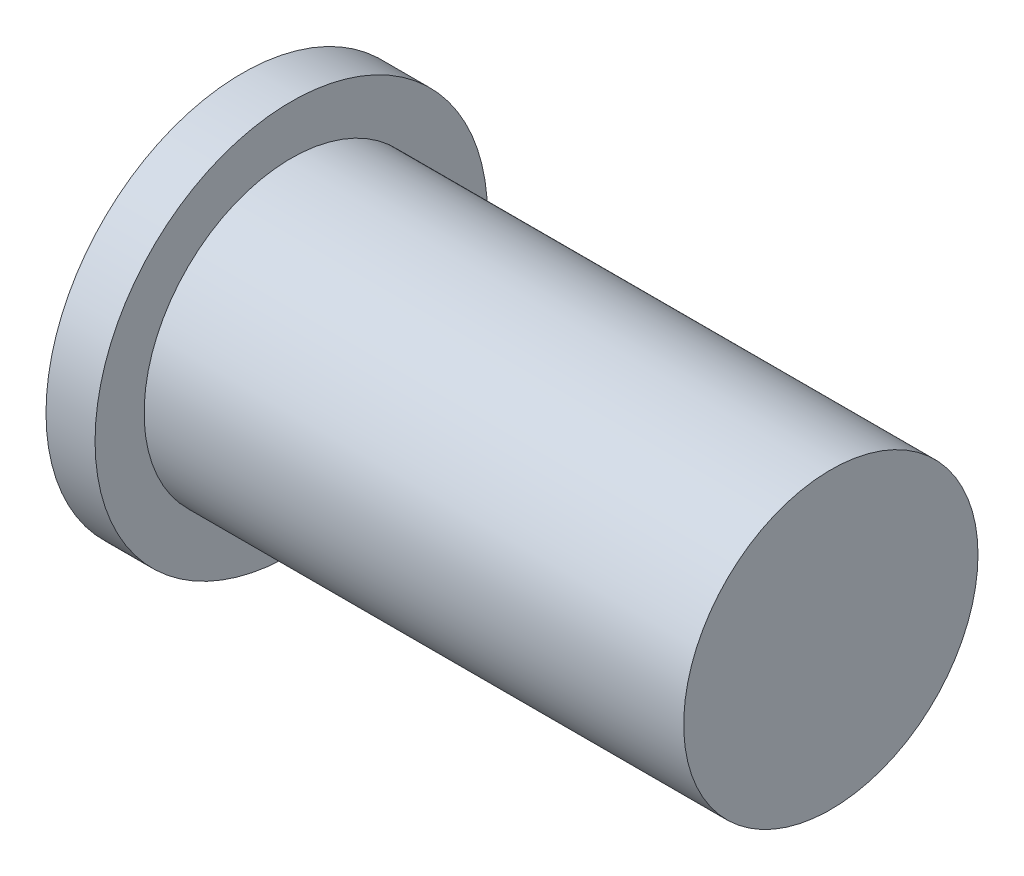
SolidWorks part; units mm, degrees
ref_plane "Front Plane" through (0, 0, 0) normal (0, 0, 1) x (1, 0, 0)
ref_plane "Top Plane" through (0, 0, 0) normal (0, 1, 0) x (1, 0, 0)
ref_plane "Right Plane" through (0, 0, 0) normal (1, 0, 0) x (0, 0, -1)
sketch "Sketch1" plane through (0, 0, 0) normal (1, 0, 0) x (0, 0, -1)
  circle A0 centre (0.1077, 0) radius 4
  circle A1 centre (0.1077, 0) radius 3
  dimension "D1" = 8
  dimension "D2" = 6
extrude "Boss-Extrude1" add sketch "Sketch1" along normal blind 1
extrude "Boss-Extrude2" add sketch "Sketch1<2>" along normal blind 12 contours A1 region at (0, 0, -0.1077)
sketch "Sketch1<2>" plane through (0, 0, 0) normal (1, 0, 0) x (0, 0, -1) same geometry as "Sketch1"
